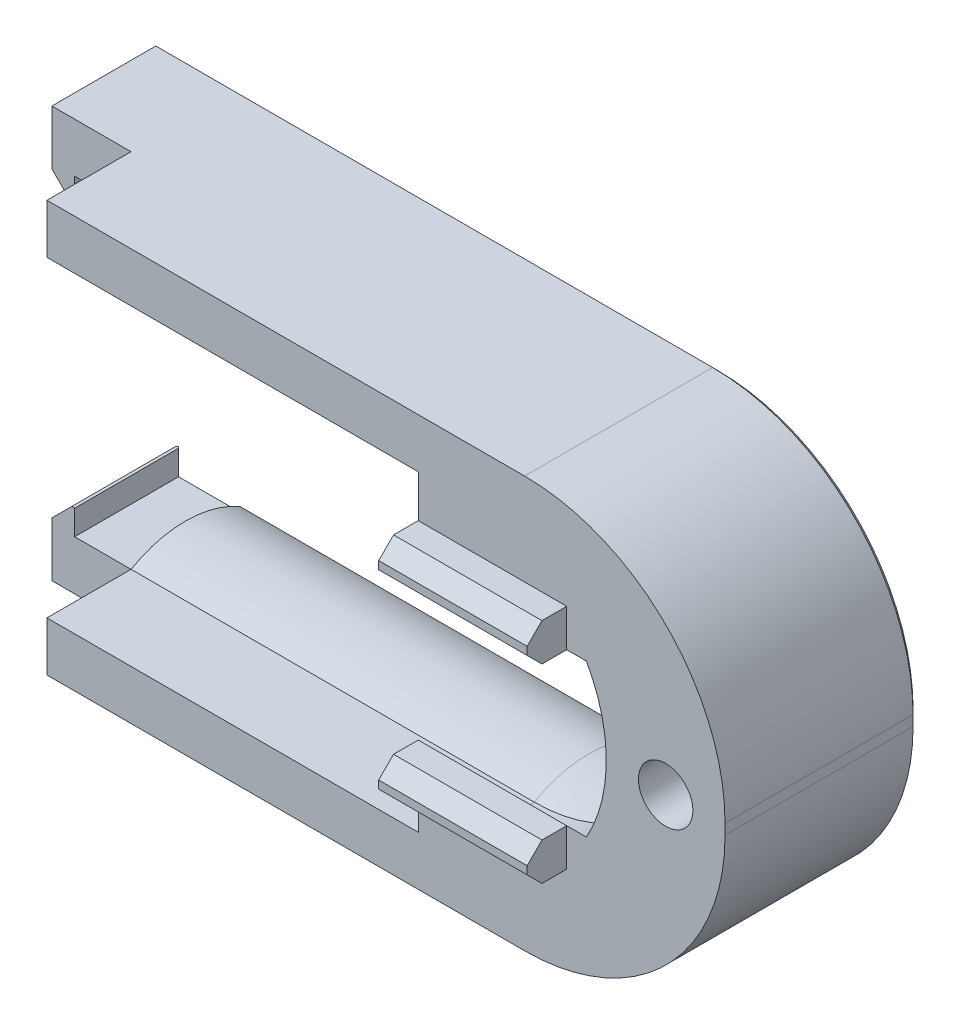
SolidWorks part; units mm, degrees
ref_plane "Top" through (0, 0, 0) normal (0, 0, 1) x (1, 0, 0)
ref_plane "Front" through (0, 0, 0) normal (0, 1, 0) x (1, 0, 0)
ref_plane "Right" through (0, 0, 0) normal (1, 0, 0) x (0, 0, -1)
sketch "Sketch1" plane through (0, 0, 0) normal (0, 0, 1) x (1, 0, 0)
  line L0 (0, 0) -> (40.75, 0)
  line L1 (40.75, 28.6) -> (0, 28.6)
  arc A0 (40.75, 0) -> (40.75, 28.6) centre (40.75, 14.3) ccw
  dimension "D1" = 28.6
  dimension "D2" = 40.75
sketch "Sketch2" plane through (0, 0, 0) normal (1, 0, 0) x (0, 0, -1)
  line L4 (-5.5, -1.4737) -> (5.5, -1.4737)
  arc A2 (-5.5, -1.4737) -> (5.5, -1.4737) centre (0, -11) cw
  dimension "D1" = 11
  dimension "D2" = 11
  dimension "D3" = 5.5
sweep "Sweep1" add profiles "Sketch2" path "Sketch1"
sketch "Sketch3" plane through (0, 0, 0) normal (0, 0, 1) x (1, 0, 0)
  line L0 (0, 30.0737) -> (0, 35.0737)
  line L1 (0, 35.0737) -> (48.2737, 35.0737)
  line L2 (68.5237, 14.8237) -> (68.5237, 13.7763)
  line L3 (48.2737, -6.4737) -> (0, -6.4737)
  line L4 (0, -6.4737) -> (0, -1.4737)
  line L5 (0, 30.0737) -> (40.75, 30.0737)
  line L6 (0, -1.4737) -> (40.75, -1.4737)
  line L7 (0, -1.4737) -> (40.75, -1.4737) construction
  arc A0 (40.75, -1.4737) -> (40.75, 30.0737) centre (40.75, 14.3) ccw construction
  arc A1 (40.75, 30.0737) -> (40.75, -1.4737) centre (40.75, 14.3) cw
  arc A2 (48.2737, -6.4737) -> (68.5237, 13.7763) centre (48.2737, 13.7763) ccw
  arc A3 (68.5237, 14.8237) -> (48.2737, 35.0737) centre (48.2737, 14.8237) ccw
  circle A4 centre (62.5237, 14.3) radius 2.75
  point P18 (56.5237, 14.3)
  dimension "D3" = 20.25
  dimension "D4" = 5.5
  dimension "D5" = 6
  dimension "D1" = 5
  dimension "D2" = 12
extrude "Boss-Extrude1" add sketch "Sketch3" along normal blind 14 and the other way blind 5.5
sketch "Sketch10" plane through (0, 0, 14) normal (0, 0, 1) x (1, 0, 0)
  line L0 (0, 30.0737) -> (40.75, 30.0737) construction
  line L1 (33.5237, 30.0737) -> (56.5237, 30.0737)
  line L2 (33.5237, 30.0737) -> (33.5237, -1.4737)
  line L3 (33.5237, -1.4737) -> (56.5237, -1.4737)
  line L4 (56.5237, 30.0737) -> (56.5237, -1.4737)
  line L5 (0, -1.4737) -> (40.75, -1.4737) construction
  arc A0 (40.75, -1.4737) -> (40.75, 30.0737) centre (40.75, 14.3) ccw construction
  dimension "D1" = 23
extrude "Boss-Extrude2" add sketch "Sketch10" against normal blind 7
hole_wizard "CBORE for M5 Hex Socket Head Cap Screw2" positions "Sketch8" profile "Sketch9" counterbore size "M5" standard "DIN" end condition through all
sketch "Sketch8" plane through (0, 0, -5.5) normal (0, 0, -1) x (-1, 0, 0)
  point P0 (-62.5237, 14.3)
sketch "Sketch9" plane through (62.5237, 14.3, -5.5) normal (1, 0, 0) x (0, 1, 0)
  line L0 (0, 0) -> (0, 19.5)
  line L1 (0, 19.5) -> (2.75, 19.5)
  line L3 (2.75, 19.5) -> (2.75, 5.4)
  line L4 (2.75, 5.4) -> (5, 5.4)
  line L5 (5, 5.4) -> (5, 0)
  line L7 (5, 0) -> (0, 0)
  line L11 (0, -6.35) -> (0, 107.95) construction
  dimension "Thru Hole Dia." = 5.5
  dimension "Thru Hole Depth" = 19.5
  dimension "C'Bore Dia." = 10
  dimension "C'Bore Depth" = 5.4
sketch "Sketch11" plane through (0, 0, 14) normal (0, 0, 1) x (1, 0, 0)
  line L1 (37.5237, 25.8) -> (52.5237, 25.8)
  line L2 (37.5237, 25.8) -> (37.5237, 22)
  line L3 (37.5237, 22) -> (52.5237, 22)
  line L4 (52.5237, 25.8) -> (52.5237, 22)
  line L5 (37.5237, 6.6) -> (52.5237, 6.6)
  line L6 (37.5237, 6.6) -> (37.5237, 2.8)
  line L7 (37.5237, 2.8) -> (52.5237, 2.8)
  line L8 (52.5237, 6.6) -> (52.5237, 2.8)
  circle A0 centre (62.5237, 14.3) radius 2.75 construction
  dimension "D1" = 10
  dimension "D2" = 15
  dimension "D3" = 3.8
  dimension "D4" = 15.4
  dimension "D5" = 7.7
extrude "Boss-Extrude3" add sketch "Sketch11" along normal blind 4
chamfer "Chamfer1" distance 1.5 angle 45 4 edges at (45.0237, 25.8, 18) (45.0237, 22, 18) (45.0237, 6.6, 18) (45.0237, 2.8, 18)
sketch "Sketch12" plane through (0, 0, 14) normal (0, 0, 1) x (1, 0, 0)
  line L0 (0, -1.4737) -> (40.75, -1.4737) construction
  line L1 (33.5237, 30.0737) -> (37.5237, 30.0737)
  line L2 (33.5237, 30.0737) -> (33.5237, -1.4737)
  line L3 (33.5237, -1.4737) -> (37.5237, -1.4737)
  line L4 (37.5237, 30.0737) -> (37.5237, -1.4737)
  line L5 (37.5237, 25.8) -> (37.5237, 22) construction
extrude "Cut-Extrude1" cut sketch "Sketch12" against normal up to surface (7 mm away) up to face at (41.0803, 14.3, 7)
sketch "Sketch13" plane through (0, 0, 14) normal (0, 0, 1) x (1, 0, 0)
  line L1 (37.5237, 22) -> (52.5237, 22)
  line L2 (37.5237, 22) -> (37.5237, 6.6)
  line L3 (37.5237, 6.6) -> (52.5237, 6.6)
  line L4 (52.5237, 22) -> (52.5237, 6.6)
extrude "Cut-Extrude2" cut sketch "Sketch13" against normal up to surface (7 mm away) up to face at (43.0803, 14.3, 7)
sketch "Sketch14" plane through (0, 0, 7) normal (0, 0, -1) x (-1, 0, 0)
  line L0 (-52.5237, 22) -> (-54.5166, 22)
  line L1 (-52.5237, 22) -> (-52.5237, 6.6)
  line L2 (-52.5237, 6.6) -> (-54.5166, 6.6)
  arc A0 (-40.75, 30.0737) -> (-40.75, -1.4737) centre (-40.75, 14.3) ccw construction
  arc A1 (-54.5166, 22) -> (-54.5166, 6.6) centre (-40.75, 14.3) ccw
extrude "Cut-Extrude3" cut sketch "Sketch14" against normal up to surface (7 mm away) up to face at (37.6358, 14.3, 14)
sketch "Sketch15" plane through (0, 0, 0) normal (-1, 0, 0) x (0, 0, 1)
  line L1 (5.5, 30.0737) -> (-5.5, 30.0737)
  line L2 (5.5, 30.0737) -> (5.5, 35.0737)
  line L3 (5.5, 35.0737) -> (-5.5, 35.0737)
  line L4 (-5.5, 30.0737) -> (-5.5, 35.0737)
extrude "Boss-Extrude4" add sketch "Sketch15" along normal blind 8
sketch "Sketch16" plane through (0, 0, -5.5) normal (0, 0, -1) x (-1, 0, 0)
  line L2 (8, 30.0737) -> (0, 30.0737) construction
  line L3 (5.7, 30.0737) -> (8, 30.0737)
  line L4 (8, 30.0737) -> (8, 27.5737)
  line L5 (8, 27.5737) -> (5.7, 27.5737)
  line L6 (5.7, 27.5737) -> (5.7, 30.0737)
  dimension "D1" = 2.3
  dimension "D2" = 2.5
extrude "Boss-Extrude5" add sketch "Sketch16" against normal up to surface (11 mm away) up to face at (-4, 32.5737, 5.5)
ref_plane "Plane1" through (0, 14.3, 0) normal (0, -1, 0) x (-1, 0, 0)
mirror "Mirror1" about plane through (0, 14.3, 0) normal (0, -1, 0) of "Boss-Extrude5", "Boss-Extrude4"
chamfer "Chamfer4" distance 2 angle 45 2 edges at (-8, 27.5737, 0) (-8, 1.0263, 0)
chamfer "Chamfer3" distance 0.5 angle 45 16 edges at (-8, 32.3237, -5.5) (20.1369, 35.0737, -5.5) (62.5926, 29.1426, -5.5) (68.5237, 14.3, -5.5) (-2.85, 30.0737, -5.5) (-5.7, 28.8237, -5.5) (-5.85, 27.5737, -5.5) (62.5926, -0.5426, -5.5) (20.1369, -6.4737, -5.5) (-8, -3.7237, -5.5) (-2.85, -1.4737, -5.5) (-5.85, 1.0263, -5.5) (-5.7, -0.2237, -5.5) (-7, 28.5737, -5.5) (-7, 0.0263, -5.5) (57.5237, 14.3, -5.5)
chamfer "Chamfer5" distance 7 angle 45 4 edges at (46.0202, 6.6, 7) (37.5237, 2.5631, 7) (46.0202, 22, 7) (37.5237, 26.0369, 7)
